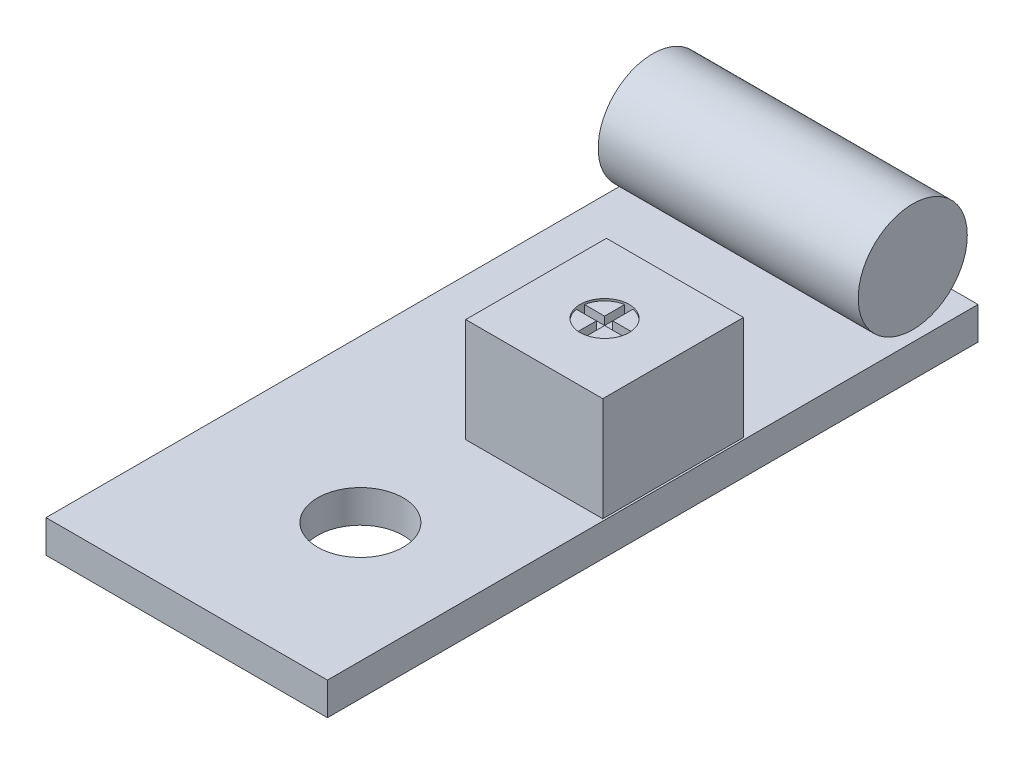
SolidWorks part; units mm, degrees
ref_plane "Front Plane" through (0, 0, 0) normal (0, 0, 1) x (1, 0, 0)
ref_plane "Top Plane" through (0, 0, 0) normal (0, 1, 0) x (1, 0, 0)
ref_plane "Right Plane" through (0, 0, 0) normal (1, 0, 0) x (0, 0, -1)
sketch "Sketch1" plane through (0, 0, 0) normal (0, 1, 0) x (1, 0, 0)
  line L0 (5.8836, -15.95) -> (5.8836, -2.35)
  line L1 (-7.9164, 15.95) -> (5.8836, 15.95)
  line L2 (-7.9164, 15.95) -> (-7.9164, -15.95)
  line L3 (-7.9164, -15.95) -> (5.8836, -15.95)
  line L4 (5.8836, 15.95) -> (5.8836, -15.95)
  line L6 (5.7836, -2.35) -> (-0.8364, -2.35)
  line L7 (5.8836, -2.35) -> (5.8836, 4.55)
  line L8 (5.7836, 4.55) -> (-0.8364, 4.55)
  line L10 (5.7836, 4.55) -> (5.7836, -2.35)
  line L11 (-0.8364, 4.55) -> (-0.9364, 4.55)
  line L12 (-0.9364, 4.55) -> (-0.9364, -2.35)
  line L13 (-0.9364, -2.35) -> (-0.8364, -2.35)
  line L14 (-0.9364, 4.55) -> (-0.8364, 4.55)
  circle A0 centre (0, -8.45) radius 2.1
  point P0 (0, 0)
  dimension "D5" = 4.2
  dimension "D1" = 31.9
  dimension "D2" = 13.8
  dimension "D3" = 13.6
  dimension "D4" = 6.9
  dimension "D6" = 6.72
  dimension "D7" = 0.1
  dimension "D8" = 0.1
extrude "Boss-Extrude1" add sketch "Sketch1" along normal blind 1.6 contours L6 L8 L4 L1 L2 L3 L0 A0 | L6 L4 L8 | A0 region at (-1.4732, 0, -0.1739) region at (2.4236, 0, -1.1) region at (0, 0, 8.45)
extrude "Cut-Extrude2" cut sketch "Sketch1<3>" along normal through all contours A0 | A0 region at (0, 0, 8.45)
sketch "Sketch1<3>" plane through (0, 0, 0) normal (0, 1, 0) x (1, 0, 0) same geometry as "Sketch1"
extrude "Boss-Extrude2" add sketch "Sketch1<4>" along normal blind 6.7 contours L12 L13 L6 L10 L8 L11
sketch "Sketch1<4>" plane through (0, 0, 0) normal (0, 1, 0) x (1, 0, 0) same geometry as "Sketch1"
ref_plane "Plane1" through (-1.0164, 0, 0) normal (1, 0, 0) x (0, 0, -1)
sketch "Sketch3" plane through (-1.0164, 0, 0) normal (1, 0, 0) x (0, 0, -1)
  line L0 (15.95, 1.6) -> (15.95, 6.95)
  line L1 (15.95, 6.95) -> (10.6, 6.95)
  circle A0 centre (13.275, 4.275) radius 2.675
  dimension "D1" = 5.35
  dimension "D2" = 5.35
extrude "Boss-Extrude3" add sketch "Sketch3" along normal blind 6.375 and the other way blind 6.375 separate body contours A0 region at (-1.0164, 4.275, -13.275)
sketch "Sketch5" plane through (0, 6.7, 0) normal (0, 1, 0) x (1, 0, 0)
  line L0 (2.2236, 1.3) -> (1.2404, 1.3)
  line L1 (2.2236, 2.2832) -> (2.2236, 1.3)
  line L2 (2.6236, 2.2832) -> (2.6236, 1.3)
  line L3 (2.2236, 0.9) -> (1.2404, 0.9)
  line L4 (3.6136, 1.2546) -> (3.6068, 1.3)
  line L5 (3.6068, 1.3) -> (2.6236, 1.3)
  line L6 (3.6068, 0.9) -> (2.6236, 0.9)
  line L7 (2.6236, 0.9) -> (2.6236, -0.0832)
  line L8 (2.2236, 0.9) -> (2.2236, -0.0832)
  circle A0 centre (2.4236, 1.1) radius 1.2
  point P11 (2.4236, 1.1)
  dimension "D1" = 2.4
extrude "Cut-Extrude7" cut sketch "Sketch5" against normal blind 0.1 contours L5 A0 L2 | L1 A0 L0 | L3 A0 L8 | L7 A0 L6 region at (1.8271, 6.7, -1.6965) region at (1.8271, 6.7, -0.5035) region at (3.0201, 6.7, -1.6965) region at (3.0201, 6.7, -0.5035)
extrude "Cut-Extrude8" cut sketch "Sketch5<3>" against normal blind 0.5 contours L6 A0 L4 L5 L2 L1 L0 L3 L8 L7 region at (2.4236, 6.7, -1.1)
sketch "Sketch5<3>" plane through (0, 6.7, 0) normal (0, 1, 0) x (1, 0, 0) same geometry as "Sketch5"
